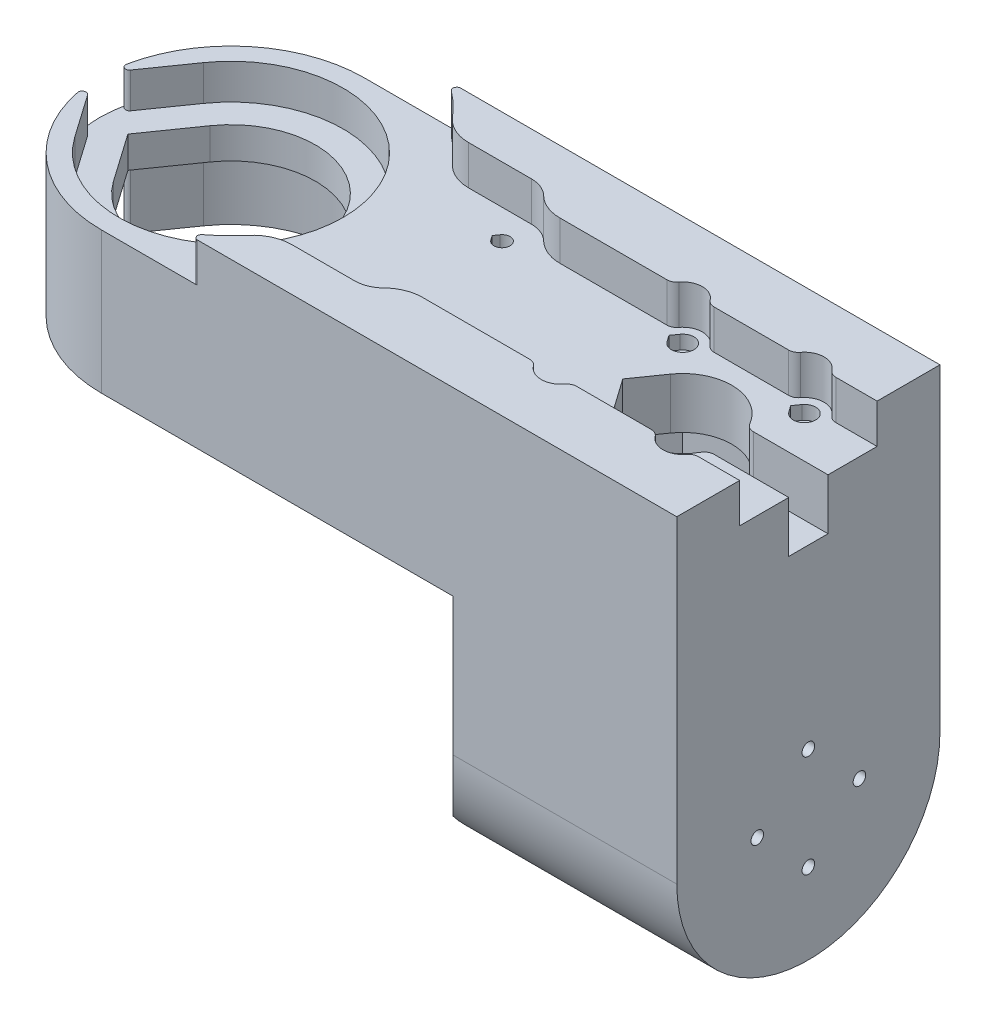
SolidWorks part; units mm, degrees
ref_plane "Front Plane" through (0, 0, 0) normal (1, 0, 0) x (0, 1, 0)
ref_plane "Top Plane" through (0, 0, 0) normal (0, 0, 1) x (0, 1, 0)
ref_plane "Right Plane" through (0, 0, 0) normal (0, 1, 0) x (-1, 0, 0)
sketch "Sketch1" plane through (0, 0, 0) normal (0, 0, 1) x (0, 1, 0)
  line L0 (45, 28.55) -> (54, 28.55)
  line L1 (-7, -93) -> (58, -93)
  line L2 (-7, -93) -> (-7, -137)
  line L3 (-7, -137) -> (58, -137)
  line L4 (58, -93) -> (58, -137)
  line L5 (59, 28.55) -> (68, 28.55)
  line L6 (59, 28.55) -> (59, -28.55)
  line L7 (59, -28.55) -> (68, -28.55)
  line L8 (68, 28.55) -> (68, -28.55)
  line L9 (45, 28.55) -> (45, -28.55)
  line L10 (45, -28.55) -> (54, -28.55)
  line L11 (54, 28.55) -> (54, -28.55)
  line L12 (-13, -147) -> (13, -147)
  line L13 (-30, 30.9464) -> (30, 30.9464) construction
  line L14 (-30, 30.9464) -> (-30, -30.2553) construction
  line L15 (-30, -30.2553) -> (30, -30.2553) construction
  line L16 (30, 30.9464) -> (30, -30.2553) construction
  line L17 (-25, -83) -> (81, -83)
  line L20 (81, -83) -> (81, -147)
  line L21 (81, -83) -> (35, -83)
  line L23 (81, 33.5) -> (35, 33.5)
  line L25 (-25, -147) -> (-13, -147)
  line L26 (-25, -147) -> (-25, -150)
  line L27 (-25, -150) -> (25, -150)
  line L28 (25, -147) -> (25, -150)
  line L29 (13, -147) -> (25, -147)
  line L30 (25, -147) -> (81, -147)
  line L31 (81, -83) -> (81, 33.5)
  line L32 (35, 33.5) -> (35, -83)
  line L33 (-25, -147) -> (-33.5, -147)
  line L34 (-25, -83) -> (-33.5, -83)
  line L35 (-33.5, -83) -> (-33.5, -147)
  point P8 (0, -30.2553)
  point P14 (68, 0)
  point P15 (58, -115)
  point P24 (45, 0)
  point P35 (0, -147)
  dimension "D1" = 65
  dimension "D2" = 44
  dimension "D3" = 57.1
  dimension "D4" = 9
  dimension "D5" = 57.1
  dimension "D6" = 9
  dimension "D7" = 115
  dimension "D8" = 60
  dimension "D9" = 5
  dimension "D10" = 15
  dimension "D11" = 10
  dimension "D12" = 3
  dimension "D13" = 50
  dimension "D14" = 26
  dimension "D15" = 10
  dimension "D16" = 23
  dimension "D17" = 4.95
  dimension "D18" = 10
  dimension "D19" = 10
  dimension "D20" = 8.5
extrude "Boss-Extrude1" add sketch "Sketch1" along normal blind 67 contours L29 L30 L20 L17 L25 L12 L1 L4 L3 L2 | L4 L1 L2 L3 | L23 L32 L17 L31 L0 L11 L10 L9 L5 L8 L7 L6 | L11 L0 L9 L10 | L8 L5 L6 L7 region at (0, 49.5, 0) region at (115, 25.5, 0) region at (0, 63.5, 0) region at (145.6883, -19, 0) region at (30.6232, 58.356, 0)
sketch "Sketch2" plane through (0, 81, 0) normal (0, 1, 0) x (-1, 0, 0)
  line L0 (-56.7259, 33.5) -> (49943.2741, 33.5) construction
  line L1 (-147, 67) -> (-147, 0) construction
  line L2 (17.6118, 21.1681) -> (26.2467, 33.5)
  line L3 (-115, -14.8158) -> (-54, -14.8158) construction
  line L4 (-93, 0) -> (-137, 0) construction
  line L5 (-93, 0) -> (-137, 0) construction
  line L9 (-147, 16) -> (-147, 51)
  line L10 (33.5473, 15.9815) -> (-147, 51) construction
  line L11 (33.5482, 51) -> (-147, 16) construction
  line L12 (-54, 18.5) -> (-54, 48.5) construction
  line L13 (-104.0826, 51) -> (-125.9174, 51)
  line L14 (-130.5, 49) -> (-99.5, 49) construction
  line L15 (-130.5, 49) -> (-130.5, 18) construction
  line L16 (-130.5, 18) -> (-99.5, 18) construction
  line L17 (-99.5, 49) -> (-99.5, 18) construction
  line L18 (-130.5, 49) -> (-99.5, 18) construction
  line L19 (-130.5, 18) -> (-99.5, 49) construction
  line L20 (-135.0826, 51) -> (-147, 51)
  line L21 (-135.0826, 16) -> (-147, 16)
  line L22 (-104.0826, 16) -> (-125.9174, 16)
  line L27 (33.5, 67) -> (-21.8575, 67)
  line L28 (33.5, 0) -> (33.5, 67)
  line L29 (33.5, 67) -> (-147, 67) construction
  line L30 (33.5, 0) -> (-21.8575, 0)
  line L31 (28.55, 0) -> (-28.55, 0) construction
  line L32 (-54, 56) -> (-33.0719, 56)
  line L33 (-54, 11) -> (-33.0719, 11)
  line L34 (23.3868, 17.1244) -> (34.8531, 33.5)
  line L35 (34.8531, 33.5) -> (23.3868, 49.8756)
  line L36 (26.2467, 33.5) -> (17.6118, 45.8319)
  line L37 (-94.9174, 16) -> (-61.0711, 16)
  line L38 (-94.9174, 51) -> (-61.0711, 51)
  arc A0 (23.3868, 49.8756) -> (23.3868, 17.1244) centre (0, 33.5) ccw
  arc A2 (-39.8663, 36.7683) -> (-39.8653, 30.2204) centre (0, 33.5) ccw
  arc A3 (-61.0711, 16) -> (-54, 11) centre (-54, 18.5) ccw
  arc A4 (-54, 56) -> (-61.0711, 51) centre (-54, 48.5) ccw
  arc A5 (-135.0826, 16) -> (-125.9174, 16) centre (-130.5, 18) ccw
  arc A6 (-104.0826, 16) -> (-94.9174, 16) centre (-99.5, 18) ccw
  arc A9 (-125.9174, 51) -> (-135.0826, 51) centre (-130.5, 49) ccw
  arc A10 (-33.0719, 11) -> (-21.8575, 0) centre (0, 33.5) ccw
  arc A11 (-94.9174, 51) -> (-104.0826, 51) centre (-99.5, 49) ccw
  arc A12 (17.6118, 45.8319) -> (17.6118, 21.1681) centre (0, 33.5) ccw
  arc A13 (17.6118, 45.8319) -> (17.6118, 21.1681) centre (0, 33.5) cw construction
  arc A14 (-21.8575, 67) -> (-33.0719, 56) centre (0, 33.5) ccw
  arc A15 (23.3868, 17.1244) -> (23.3868, 49.8756) centre (0, 33.5) ccw construction
  point P4 (-56.7259, 33.5)
  point P9 (-56.75, 33.4953)
  point P23 (-115, 33.5)
  point P39 (33.5, 33.5)
  point P61 (-54, 33.5)
  dimension "D1" = 57.1
  dimension "D2" = 35
  dimension "D3" = 80
  dimension "D6" = 15
  dimension "D7" = 15
  dimension "D9" = 10
  dimension "D10" = 43
  dimension "D11" = 55
  dimension "D12" = 10
  dimension "D4" = 61
  dimension "D5" = 30
  dimension "D8" = 31
  dimension "D13" = 55
extrude "Cut-Extrude1" cut sketch "Sketch2" against normal through all both and the other way through all contours A12 L2 L36
fillet "Fillet3" radius 34 2 edges at (-33.5, 58, 0) (-33.5, 58, 67)
extrude "Cut-Extrude2" cut sketch "Sketch2<4>" against normal blind 10 and the other way through all contours L20 L9 L21 A5 L22 A6 L37 A3 L33 A10 L30 L28 L27 A14 L32 A4 L38 A11 L13 A9
sketch "Sketch2<4>" plane through (0, 81, 0) normal (0, 1, 0) x (-1, 0, 0) same geometry as "Sketch2"
extrude "Cut-Extrude3" cut sketch "Sketch2<5>" against normal blind 9 from surface contours A0 L34 L35 starting at face at (71.9263, 71, 33.5)
sketch "Sketch2<5>" plane through (0, 81, 0) normal (0, 1, 0) x (-1, 0, 0) same geometry as "Sketch2"
extrude "Cut-Extrude4" cut sketch "Sketch2<6>" along normal blind 19 from surface contours A0 L34 L35 starting at face at (-7.4528, 35, 33.5)
sketch "Sketch2<6>" plane through (0, 81, 0) normal (0, 1, 0) x (-1, 0, 0) same geometry as "Sketch2"
sketch "Sketch3" plane through (0, 71, 0) normal (0, 1, 0) x (-1, 0, 0)
  line L0 (-93, 0) -> (-137, 0) construction
  line L1 (-93, 0) -> (-137, 0)
  line L2 (-115, 33.5) -> (-50115, 33.5) construction
  line L4 (-99.7403, 33.5) -> (-104.3338, 40.0179)
  line L5 (-127.65, 49) -> (-127, 49) construction
  line L6 (-130.5, 49) -> (-99.5, 49) construction
  line L7 (-130.5, 49) -> (-130.5, 18) construction
  line L8 (-130.5, 18) -> (-99.5, 18) construction
  line L9 (-99.5, 49) -> (-99.5, 18) construction
  line L12 (-128.9, 49) -> (-128.5, 49) construction
  line L13 (-129.22, 49.96) -> (-128.5, 49)
  line L14 (-129.22, 48.04) -> (-128.5, 49)
  line L15 (-128.1793, 50.6543) -> (-127, 49)
  line L16 (-127, 49) -> (-128.1793, 47.3457)
  line L17 (-96, 49) -> (-97.1793, 47.3457)
  line L18 (-97.1793, 50.6543) -> (-96, 49)
  line L19 (-98.22, 48.04) -> (-97.5, 49)
  line L20 (-98.22, 49.96) -> (-97.5, 49)
  line L21 (-96, 18) -> (-97.1793, 16.3457)
  line L22 (-97.1793, 19.6543) -> (-96, 18)
  line L23 (-98.22, 17.04) -> (-97.5, 18)
  line L24 (-98.22, 18.96) -> (-97.5, 18)
  line L25 (-127, 18) -> (-128.1793, 16.3457)
  line L26 (-128.1793, 19.6543) -> (-127, 18)
  line L27 (-129.22, 17.04) -> (-128.5, 18)
  line L28 (-129.22, 18.96) -> (-128.5, 18)
  line L29 (-115, 0) -> (-115, 33.5) construction
  line L30 (-147, 38.5) -> (-126.4564, 38.5)
  line L32 (-147, 28.5) -> (-126.4564, 28.5)
  line L34 (-167.5436, 38.5) -> (-126.4564, 28.5) construction
  line L35 (-167.5436, 28.5) -> (-126.4564, 38.5) construction
  line L36 (-147, 38.5) -> (-147, 28.5)
  line L38 (-104.7606, 26.3303) -> (-99.7403, 33.5)
  arc A0 (-128.1793, 50.6543) -> (-128.1793, 47.3457) centre (-130.5, 49) ccw
  arc A1 (-129.22, 49.96) -> (-129.22, 48.04) centre (-130.5, 49) ccw
  arc A2 (-129.22, 49.96) -> (-129.22, 48.04) centre (-130.5, 49) cw construction
  arc A3 (-128.1793, 50.6543) -> (-133.0893, 47.8092) centre (-130.5, 49) cw construction
  arc A4 (-97.1793, 50.6543) -> (-97.1793, 47.3457) centre (-99.5, 49) ccw
  arc A5 (-98.22, 49.96) -> (-98.22, 48.04) centre (-99.5, 49) ccw
  arc A6 (-98.22, 49.96) -> (-98.22, 48.04) centre (-99.5, 49) cw construction
  arc A7 (-97.1793, 50.6543) -> (-102.0893, 47.8092) centre (-99.5, 49) cw construction
  arc A8 (-97.1793, 19.6543) -> (-97.1793, 16.3457) centre (-99.5, 18) ccw
  arc A9 (-98.22, 18.96) -> (-98.22, 17.04) centre (-99.5, 18) ccw
  arc A10 (-98.22, 18.96) -> (-98.22, 17.04) centre (-99.5, 18) cw construction
  arc A11 (-97.1793, 19.6543) -> (-102.0893, 16.8092) centre (-99.5, 18) cw construction
  arc A12 (-128.1793, 19.6543) -> (-128.1793, 16.3457) centre (-130.5, 18) ccw
  arc A13 (-129.22, 18.96) -> (-129.22, 17.04) centre (-130.5, 18) ccw
  arc A14 (-129.22, 18.96) -> (-129.22, 17.04) centre (-130.5, 18) cw construction
  arc A15 (-128.1793, 19.6543) -> (-133.0893, 16.8092) centre (-130.5, 18) cw construction
  arc A18 (-126.4564, 28.5) -> (-104.7606, 26.3303) centre (-115, 33.5) ccw
  arc A19 (-104.3338, 40.0179) -> (-126.4564, 38.5) centre (-115, 33.5) ccw
  arc A20 (-104.3338, 40.0179) -> (-104.7606, 26.3303) centre (-115, 33.5) cw construction
  point P8 (-115, 33.5)
  point P24 (-147, 33.5)
  point P63 (-115, 49)
  dimension "D2" = 5.7
  dimension "D3" = 3.2
  dimension "D8" = 25
  dimension "D1" = 31
  dimension "D4" = 0.65
  dimension "D5" = 0.4
  dimension "D9" = 10
  dimension "D6" = 2
  dimension "D7" = 2
extrude "Cut-Extrude5" cut sketch "Sketch3" against normal up to vertex (13 mm away) contours L32 A18 L38 L4 A19 L30 L36 | A13 L27 L28 | A9 L23 L24 | A5 L19 L20 | A1 L14 L13 up to point (137, 58, 0)
extrude "Cut-Extrude6" cut sketch "Sketch3<3>" against normal blind 3.5 contours A0 L16 L15 | A12 L25 L26 | A4 L17 L18 | A8 L21 L22
sketch "Sketch3<3>" plane through (0, 71, 0) normal (0, 1, 0) x (-1, 0, 0) same geometry as "Sketch3"
sketch "Sketch4" plane through (0, 71, 0) normal (0, 1, 0) x (-1, 0, 0)
  line L0 (-115, 33.5) -> (-54, 33.5) construction
  line L1 (-54, 48.5) -> (-54, 18.5) construction
  line L2 (-52.6894, 49.4177) -> (-52.0468, 48.5)
  line L3 (-52.6894, 47.5823) -> (-52.0468, 48.5)
  line L4 (-52.0468, 48.5) -> (-52.4, 48.5) construction
  line L7 (-52.6894, 19.4177) -> (-52.0468, 18.5)
  line L8 (-51.95, 48.5) -> (-51.4974, 48.5) construction
  line L9 (-51.4974, 48.5) -> (-52.3207, 47.3242)
  line L10 (-52.3207, 49.6758) -> (-51.4974, 48.5)
  line L11 (-52.6894, 17.5823) -> (-52.0468, 18.5)
  line L12 (-52.0468, 18.5) -> (-52.4, 18.5) construction
  line L13 (-52.9972, 18.5) -> (-51.4974, 18.5) construction
  line L14 (-51.4974, 18.5) -> (-52.3207, 17.3242)
  line L15 (-52.3207, 19.6758) -> (-51.4974, 18.5)
  arc A1 (-52.6894, 49.4177) -> (-52.6894, 47.5823) centre (-54, 48.5) ccw
  arc A2 (-52.6894, 49.4177) -> (-52.6894, 47.5823) centre (-54, 48.5) cw construction
  arc A4 (-52.6894, 19.4177) -> (-52.6894, 17.5823) centre (-54, 18.5) ccw
  arc A5 (-52.3207, 49.6758) -> (-52.3207, 47.3242) centre (-54, 48.5) ccw
  arc A6 (-52.3207, 49.6758) -> (-52.3207, 47.3242) centre (-54, 48.5) cw construction
  arc A7 (-52.6894, 19.4177) -> (-52.6894, 17.5823) centre (-54, 18.5) cw construction
  arc A8 (-52.3207, 19.6758) -> (-52.3207, 17.3242) centre (-54, 18.5) ccw
  arc A9 (-52.3207, 19.6758) -> (-52.3207, 17.3242) centre (-54, 18.5) cw construction
  point P5 (-54, 33.5)
  dimension "D3" = 3.2
  dimension "D5" = 3.2
  dimension "D7" = 4.1
  dimension "D6" = 4.1
  dimension "D1" = 61
  dimension "D2" = 30
  dimension "D4" = 55
  dimension "D8" = 55
  dimension "D9" = 55
  dimension "D10" = 55
extrude "Cut-Extrude7" cut sketch "Sketch4" against normal blind 10 contours A1 L3 L2 | A4 L11 L7
extrude "Cut-Extrude8" cut sketch "Sketch4<3>" against normal blind 7
sketch "Sketch4<3>" plane through (0, 71, 0) normal (0, 1, 0) x (-1, 0, 0) same geometry as "Sketch4"
sketch "Sketch6" plane through (0, 35, 0) normal (0, -1, 0) x (1, 0, 0)
  line L0 (0, 33.5) -> (-26.2467, 33.5) construction
  line L1 (0, 33.5) -> (25.8751, 21.4342) construction
  line L2 (25.8751, 21.4342) -> (39.4317, 21.4342) construction
  line L3 (39.4317, 21.4342) -> (39.4317, 46.3342) construction
  line L4 (39.4317, 46.3342) -> (39.4317, 51.5342) construction
  line L5 (39.4317, 21.4342) -> (39.4317, 16.3342) construction
  line L6 (39.4317, 16.3342) -> (39.4317, 11.1342) construction
  line L9 (61.3317, 33.5) -> (83, 33.5) construction
  line L10 (83, 36) -> (83, 31)
  line L13 (38.1211, 15.4165) -> (37.4785, 16.3342)
  line L14 (38.1211, 17.252) -> (37.4785, 16.3342)
  line L15 (37.4785, 16.3342) -> (37.8317, 16.3342) construction
  line L16 (37.3817, 16.3342) -> (36.9291, 16.3342) construction
  line L17 (36.9291, 16.3342) -> (37.7525, 17.5101)
  line L18 (37.7525, 15.1584) -> (36.9291, 16.3342)
  line L19 (38.1211, 45.4165) -> (37.4785, 46.3342)
  line L20 (38.1211, 47.252) -> (37.4785, 46.3342)
  line L21 (37.4785, 46.3342) -> (37.8317, 46.3342) construction
  line L22 (37.3817, 46.3342) -> (36.9291, 46.3342) construction
  line L23 (36.9291, 46.3342) -> (37.7525, 47.5101)
  line L24 (37.7525, 45.1584) -> (36.9291, 46.3342)
  line L25 (39.4317, 51.5342) -> (22.133, 51.5342)
  line L26 (39.4317, 11.1342) -> (17.7447, 11.1342)
  line L27 (39.4317, 11.1342) -> (46.3317, 11.1342)
  line L28 (39.4317, 51.5342) -> (46.3317, 51.5342)
  line L29 (46.3317, 51.5342) -> (46.3317, 43.5)
  line L30 (46.3317, 33.5) -> (61.3317, 33.5) construction
  line L31 (46.3317, 23.5) -> (46.3317, 11.1342)
  line L33 (46.3317, 23.5) -> (51.3317, 23.5)
  line L34 (46.3317, 43.5) -> (51.3317, 43.5)
  line L36 (51.3317, 23.5) -> (61.3317, 31)
  line L37 (51.3317, 43.5) -> (61.3317, 36)
  line L41 (61.3317, 36) -> (83, 36)
  line L42 (61.3317, 31) -> (83, 31)
  arc A0 (-23.3868, 17.1244) -> (-23.3868, 49.8756) centre (0, 33.5) ccw construction
  arc A5 (38.1211, 15.4165) -> (38.1211, 17.252) centre (39.4317, 16.3342) ccw
  arc A6 (38.1211, 15.4165) -> (38.1211, 17.252) centre (39.4317, 16.3342) cw construction
  arc A7 (37.7525, 15.1584) -> (37.7525, 17.5101) centre (39.4317, 16.3342) ccw
  arc A8 (37.7525, 15.1584) -> (37.7525, 17.5101) centre (39.4317, 16.3342) cw construction
  arc A9 (38.1211, 45.4165) -> (38.1211, 47.252) centre (39.4317, 46.3342) ccw
  arc A10 (38.1211, 45.4165) -> (38.1211, 47.252) centre (39.4317, 46.3342) cw construction
  arc A11 (37.7525, 45.1584) -> (37.7525, 47.5101) centre (39.4317, 46.3342) ccw
  arc A12 (37.7525, 45.1584) -> (37.7525, 47.5101) centre (39.4317, 46.3342) cw construction
  arc A13 (-23.3868, 17.1244) -> (-23.3868, 49.8756) centre (0, 33.5) ccw construction
  arc A14 (22.133, 51.5342) -> (17.7447, 11.1342) centre (0, 33.5) cw
  point P17 (72.1659, 33.5)
  dimension "D7" = 2.5
  dimension "D11" = 3.2
  dimension "D12" = 4.1
  dimension "D15" = 3.2
  dimension "D16" = 4.1
  dimension "D1" = 155
  dimension "D2" = 24.9
  dimension "D3" = 13.5566
  dimension "D4" = 5.2
  dimension "D5" = 5.2
  dimension "D6" = 5.1
  dimension "D13" = 55
  dimension "D14" = 55
  dimension "D17" = 55
  dimension "D18" = 55
  dimension "D19" = 6.9
  dimension "D20" = 20
  dimension "D21" = 15
  dimension "D22" = 5
  dimension "D23" = 5
sketch "Sketch10" plane through (0, -33.5, 0) normal (0, -1, 0) x (1, 0, 0)
  line L0 (83, 67) -> (147, 0) construction
  line L1 (83, 0) -> (147, 67) construction
  line L2 (83, 0) -> (147, 0) construction
  line L3 (93, 55.5) -> (137, 55.5)
  line L4 (93, 11.5) -> (137, 11.5)
  line L5 (137, 55.5) -> (137, 11.5)
  line L6 (93, 55.5) -> (137, 11.5) construction
  line L7 (93, 11.5) -> (137, 55.5) construction
  line L8 (93, 55.5) -> (93, 43.5)
  line L9 (137, 33.5) -> (83, 33.5) construction
  line L10 (83, 43.5) -> (83, 23.5)
  line L11 (83, 23.5) -> (93, 23.5)
  line L12 (83, 43.5) -> (93, 43.5)
  line L13 (93, 23.5) -> (93, 11.5)
  point P9 (115, 33.5)
  point P10 (115, 33.5)
  point P20 (83, 33.5)
  dimension "D1" = 44
  dimension "D2" = 20
extrude "Cut-Extrude18" cut sketch "Sketch10" against normal up to surface (91.5 mm away) up to face at (122.4062, 58, 33.4581)
extrude "Cut-Extrude11" cut sketch "Sketch6" against normal blind 10 contours L33 L36 L42 L10 L41 L37 L34 L29 L28 L25 A14 L26 L27 L31
extrude "Cut-Extrude12" cut sketch "Sketch6<4>" against normal blind 7 from surface contours A7 L17 L18 | A11 L23 L24 starting at face at (52.0813, 45, 32.7016)
sketch "Sketch6<4>" plane through (0, 35, 0) normal (0, -1, 0) x (1, 0, 0) same geometry as "Sketch6"
extrude "Cut-Extrude13" cut sketch "Sketch6<5>" against normal blind 3 from surface contours A5 L14 L13 | A9 L20 L19 starting at face at (38.7211, 52, 46.3342)
sketch "Sketch6<5>" plane through (0, 35, 0) normal (0, -1, 0) x (1, 0, 0) same geometry as "Sketch6"
fillet "Fillet5" radius 2.5 6 edges at (46.3317, 40, 43.5) (46.3317, 40, 23.5) (51.3317, 40, 43.5) (61.3317, 40, 36) (61.3317, 40, 31) (51.3317, 40, 23.5)
fillet "Fillet1" radius 10 4 edges at (61.0711, 76, 51) (61.0711, 76, 16) (33.0719, 76, 56) (33.0719, 76, 11)
fillet "Fillet2" radius 2.5 10 edges at (135.0826, 76, 16) (125.9174, 76, 16) (104.0826, 76, 16) (104.0826, 76, 51) (125.9174, 76, 51) (135.0826, 76, 51) (126.4564, 64.5, 28.5) (126.4564, 64.5, 38.5) (94.9174, 76, 51) (94.9174, 76, 16)
fillet "Fillet4" radius 1 6 edges at (-33.4026, 44.5, 31.4285) (-33.4026, 44.5, 35.5715) (-33.4026, 66.5, 35.5715) (-33.4026, 66.5, 31.4285) (21.8575, 76, 67) (21.8575, 76, 0)
chamfer "Chamfer7" distance 12 angle 45 2 edges at (93, 12.25, 43.5) (93, 12.25, 23.5)
chamfer "Chamfer5" distance 9.5 angle 45 2 edges at (83, 40, 36) (83, 40, 31)
sketch "Sketch11" plane through (137, 0, 0) normal (-1, 0, 0) x (0, -1, 0)
  line L0 (-71, 33.5) -> (-50071, 33.5) construction
  circle A0 centre (0, 33.5) radius 13 construction
  circle A1 centre (0, 33.5) radius 25
  circle A2 centre (0, 46.5) radius 1.6
  circle A3 centre (0, 46.5) radius 2.85
  circle A4 centre (13, 33.5) radius 2.85
  circle A5 centre (13, 33.5) radius 1.6
  circle A6 centre (0, 20.5) radius 2.85
  circle A7 centre (0, 20.5) radius 1.6
  circle A8 centre (-13, 33.5) radius 2.85
  circle A9 centre (-13, 33.5) radius 1.6
  dimension "D1" = 50
  dimension "D2" = 26
  dimension "D3" = 3.2
  dimension "D4" = 5.7
extrude "Cut-Extrude19" cut sketch "Sketch11" against normal through all contours A9 | A2 | A5 | A7
extrude "Cut-Extrude20" cut sketch "Sketch11<3>" against normal blind 3.5 contours A8 | A3 | A4 | A6
sketch "Sketch11<3>" plane through (137, 0, 0) normal (-1, 0, 0) x (0, -1, 0) same geometry as "Sketch11"
chamfer "Chamfer6" distance 7 angle 45 2 edges at (83, 0.75, 0) (83, 0.75, 67)
sketch "Sketch9" plane through (147, 0, 0) normal (1, 0, 0) x (0, 1, 0)
  line L0 (71, 33.5) -> (-49929, 33.5) construction
  line L2 (0, 67) -> (-54.5324, 67)
  line L4 (-54.5324, 67) -> (-54.5324, 0)
  line L5 (-54.5324, 0) -> (0, 0)
  arc A3 (0, 67) -> (0, 0) centre (0, 33.5) ccw
extrude "Cut-Extrude16" cut sketch "Sketch9" against normal up to surface (64 mm away) up to face at (83, 0.75, 52.75)
chamfer "Chamfer8" distance 5 angle 45 2 edges at (83, 1.8615, 45.5) (83, 1.8615, 21.5) first distance on face at (86.3773, 23.1701, 48.8773) first distance on face at (86.3773, 23.1701, 18.1227)
sketch "Sketch12" plane through (83, 0, 0) normal (-1, 0, 0) x (0, -1, 0)
  line L0 (25.2636, 55.5) -> (25.2636, 11.5)
  arc A0 (25.2636, 11.5) -> (25.2636, 55.5) centre (0, 33.5) ccw construction
  arc A1 (25.2636, 11.5) -> (25.2636, 55.5) centre (0, 33.5) ccw
extrude "Cut-Extrude21" cut sketch "Sketch12" against normal up to vertex (10 mm away) up to point (93, -25.2636, 11.5)
